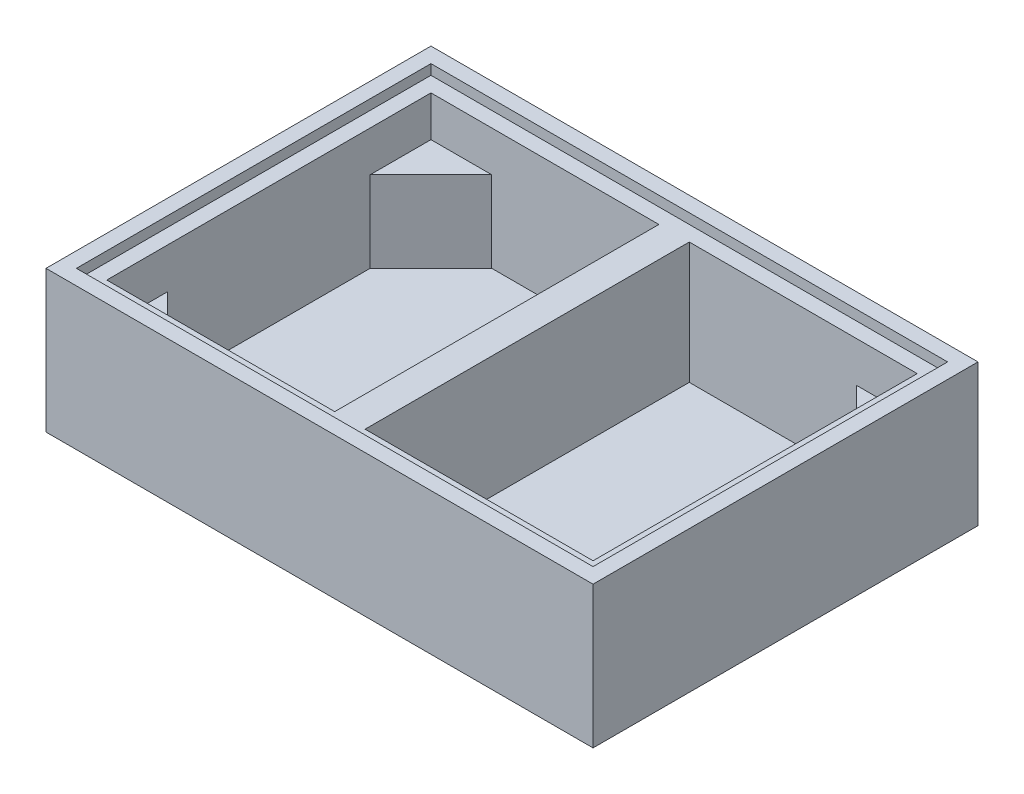
SolidWorks part; units mm, degrees
ref_plane "Front Plane" through (0, 0, 0) normal (0, 0, 1) x (1, 0, 0)
ref_plane "Top Plane" through (0, 0, 0) normal (0, 1, 0) x (1, 0, 0)
ref_plane "Right Plane" through (0, 0, 0) normal (1, 0, 0) x (0, 0, -1)
sketch "Sketch1" plane through (0, 0, 0) normal (0, 1, 0) x (1, 0, 0)
  line L1 (0, 0) -> (540, 0)
  line L2 (0, 0) -> (0, 380)
  line L3 (0, 380) -> (540, 380)
  line L4 (540, 0) -> (540, 380)
  dimension "D1" = 540
  dimension "D2" = 380
extrude "Boss-Extrude1" add sketch "Sketch1" against normal blind 140
sketch "Sketch3" plane through (0, 0, 0) normal (0, 1, 0) x (1, 0, 0)
  line L0 (540, 380) -> (0, 380) construction
  line L1 (15, 365) -> (525, 365)
  line L2 (15, 365) -> (15, 15)
  line L3 (15, 15) -> (525, 15)
  line L4 (525, 365) -> (525, 15)
  line L5 (0, 380) -> (0, 0) construction
  line L6 (0, 0) -> (540, 0) construction
  line L7 (540, 0) -> (540, 380) construction
  dimension "D1" = 15
  dimension "D2" = 15
  dimension "D3" = 15
  dimension "D4" = 15
extrude "Cut-Extrude1" cut sketch "Sketch3" against normal blind 10
sketch "Sketch2" plane through (0, -10, 0) normal (0, 1, 0) x (1, 0, 0)
  line L0 (540, 380) -> (0, 380) construction
  line L1 (30, 350) -> (255, 350)
  line L2 (30, 350) -> (30, 30)
  line L3 (30, 30) -> (255, 30)
  line L4 (255, 350) -> (255, 30)
  line L5 (0, 380) -> (0, 0) construction
  line L6 (0, 0) -> (540, 0) construction
  line L7 (270, 380) -> (270, 0) construction
  line L8 (510, 30) -> (285, 30)
  line L9 (285, 350) -> (285, 30)
  line L10 (510, 350) -> (285, 350)
  line L11 (510, 350) -> (510, 30)
  dimension "D1" = 30
  dimension "D2" = 30
  dimension "D3" = 30
  dimension "D4" = 255
extrude "Cut-Extrude2" cut sketch "Sketch2" against normal blind 40
sketch "Sketch5" plane through (0, -50, 0) normal (0, 1, 0) x (1, 0, 0)
  line L0 (30, 290) -> (90, 350)
  line L1 (30, 350) -> (30, 30) construction
  line L2 (255, 350) -> (30, 350) construction
  line L5 (255, 350) -> (30, 350) construction
  line L6 (255, 350) -> (90, 350)
  line L7 (270, 365) -> (270, 0) construction
  line L8 (525, 365) -> (15, 365) construction
  line L9 (0, 0) -> (540, 0) construction
  line L10 (0, 190) -> (540, 190) construction
  line L11 (0, 380) -> (0, 0) construction
  line L12 (540, 0) -> (540, 380) construction
  line L13 (30, 90) -> (90, 30)
  line L18 (510, 90) -> (450, 30)
  line L21 (510, 290) -> (450, 350)
  line L22 (510, 30) -> (510, 350) construction
  line L23 (285, 30) -> (510, 30) construction
  line L24 (510, 350) -> (285, 350) construction
  line L25 (285, 350) -> (285, 30) construction
  line L26 (255, 30) -> (255, 350) construction
  line L27 (30, 30) -> (255, 30) construction
  line L28 (30, 290) -> (30, 90)
  line L29 (510, 90) -> (510, 290)
  line L30 (285, 30) -> (450, 30)
  line L31 (450, 350) -> (285, 350)
  line L32 (285, 350) -> (285, 30)
  line L33 (255, 30) -> (255, 350)
  line L34 (90, 30) -> (255, 30)
  dimension "D1" = 60
  dimension "D2" = 60
extrude "Cut-Extrude3" cut sketch "Sketch5" against normal blind 80
